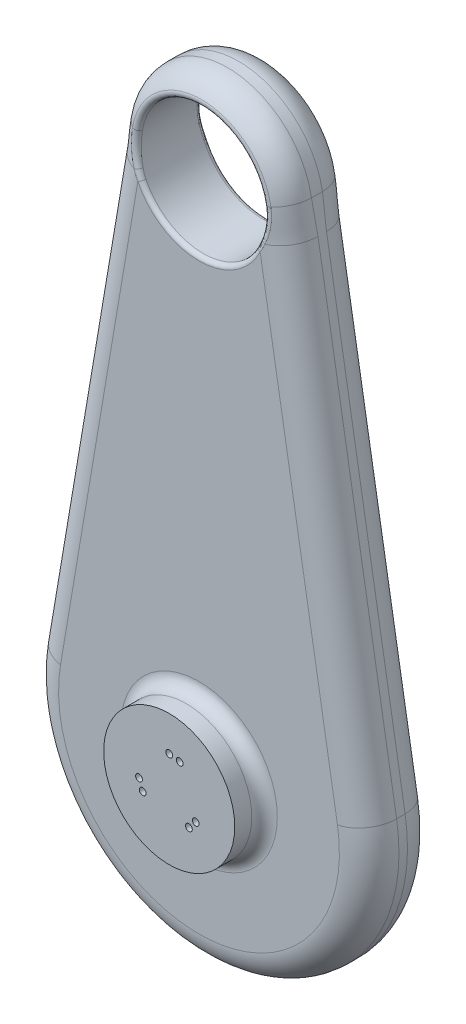
SolidWorks part; units mm, degrees
material "Gray Cast Iron"
ref_plane "Front Plane" through (0, 0, 0) normal (0, 0, 1) x (1, 0, 0)
ref_plane "Top Plane" through (0, 0, 0) normal (0, 1, 0) x (1, 0, 0)
ref_plane "Right Plane" through (0, 0, 0) normal (1, 0, 0) x (0, 0, -1)
sketch "Sketch1" plane through (0, 0, 0) normal (0, 0, 1) x (1, 0, 0)
  line L0 (-197.2027, 33.3333) -> (-98.6013, 616.6667)
  line L1 (197.2027, 33.3333) -> (98.6013, 616.6667)
  line L2 (0, 600) -> (0, 0) construction
  circle A0 centre (0, 0) radius 77
  circle A1 centre (0, 600) radius 75
  arc A2 (-197.2027, 33.3333) -> (197.2027, 33.3333) centre (0, 0) ccw
  arc A3 (98.6013, 616.6667) -> (-98.6013, 616.6667) centre (0, 600) ccw
  dimension "D1" = 154
  dimension "D2" = 400
  dimension "D3" = 150
  dimension "D4" = 200
  dimension "D5" = 600
extrude "Boss-Extrude1" add sketch "Sketch1" against normal blind 80
extrude "Boss-Extrude3" add sketch "Sketch1<4>" along normal blind 35 and the other way through all contours A0 region at (0, 0, 0)
sketch "Sketch1<4>" plane through (0, 0, 0) normal (0, 0, 1) x (1, 0, 0) same geometry as "Sketch1"
sketch "Sketch2" plane through (0, 0, 35) normal (0, 0, 1) x (1, 0, 0)
  line L0 (0, 0) -> (0, 36) construction
  circle A5 centre (12.3127, 33.8289) radius 4
  circle A6 centre (0, 36) radius 4
  circle A7 centre (0, 0) radius 36 construction
  circle A8 centre (31.1769, -18) radius 4
  circle A9 centre (23.1404, -27.5776) radius 4
  circle A10 centre (-31.1769, -18) radius 4
  circle A11 centre (-35.4531, -6.2513) radius 4
  dimension "D2" = 8
  dimension "D3" = 8
  dimension "D1" = 12.5027
  dimension "D4" = 3
extrude "Cut-Extrude1" cut sketch "Sketch2" against normal through all
fillet "Fillet2" radius 35 6 edges at (147.902, 325, 0) (0, -200, 0) (147.902, 325, -80) (0, -200, -80) (-147.902, 325, 0) (-147.902, 325, -80)
fillet "Fillet3" radius 15 1 edges at (77, 0, 0)
fillet "Fillet4" radius 5 8 edges at (0, 675, -80) (74.6709, 592.9821, -80) (0, 525, -80) (-74.6709, 592.9821, -80) (74.6709, 592.9821, 0) (0, 525, 0) (-74.6709, 592.9821, 0) (0, 675, 0)
